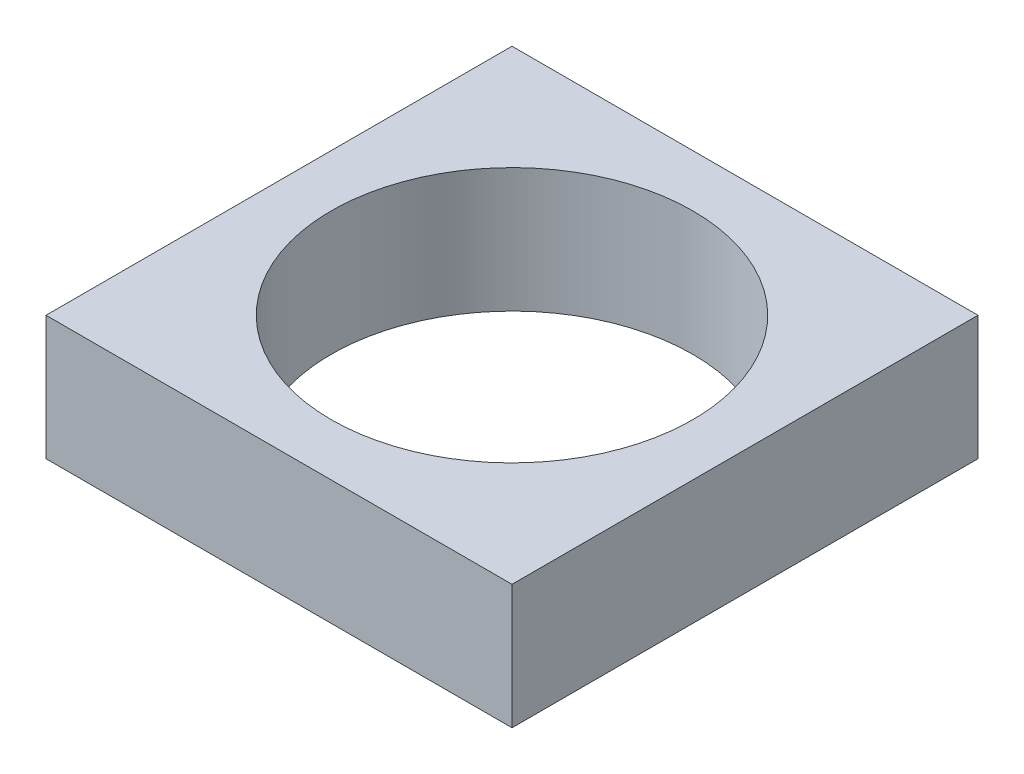
SolidWorks part; units mm, degrees
ref_plane "Front Plane" through (0, 0, 0) normal (0, 0, 1) x (1, 0, 0)
ref_plane "Top Plane" through (0, 0, 0) normal (0, 1, 0) x (1, 0, 0)
ref_plane "Right Plane" through (0, 0, 0) normal (1, 0, 0) x (0, 0, -1)
sketch "Sketch1" plane through (0, 0, 0) normal (0, 1, 0) x (1, 0, 0)
  line L1 (-22.5, -22.5) -> (22.5, -22.5)
  line L2 (-22.5, -22.5) -> (-22.5, 22.5)
  line L3 (-22.5, 22.5) -> (22.5, 22.5)
  line L4 (22.5, -22.5) -> (22.5, 22.5)
  line L5 (-22.5, -22.5) -> (22.5, 22.5) construction
  line L6 (-22.5, 22.5) -> (22.5, -22.5) construction
  circle A0 centre (0, 0) radius 17.4625
  point P0 (0, 0)
  dimension "D2" = 34.925
  dimension "D1" = 45
extrude "Boss-Extrude1" add sketch "Sketch1" along normal blind 12
